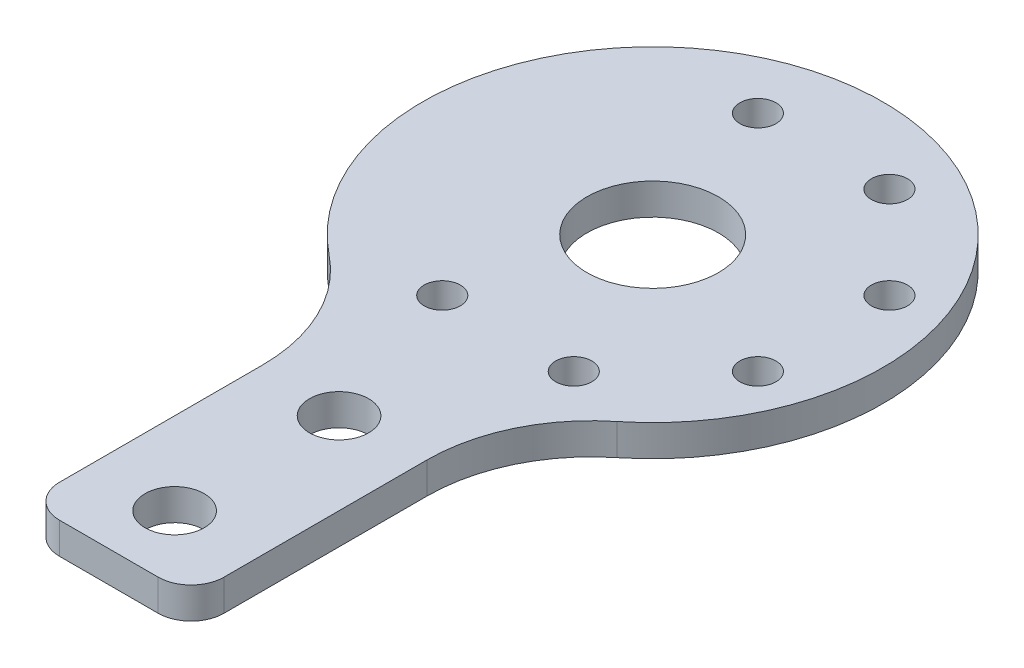
SolidWorks part; units mm, degrees
material "1060 Alloy"
ref_plane "Front Plane" through (0, 0, 0) normal (0, 0, 1) x (1, 0, 0)
ref_plane "Top Plane" through (0, 0, 0) normal (0, 1, 0) x (1, 0, 0)
ref_plane "Right Plane" through (0, 0, 0) normal (1, 0, 0) x (0, 0, -1)
sketch "Sketch1" plane through (0, 0, 0) normal (0, 1, 0) x (1, 0, 0)
  line L0 (-12.5, -82.6917) -> (12.5, -82.6917)
  line L1 (12.5, -82.6917) -> (12.5, -32.6917)
  line L2 (-12.5, -82.6917) -> (-12.5, -32.6917)
  arc A0 (12.5, -32.6917) -> (-12.5, -32.6917) centre (0, 0) ccw
  point P5 (0, -82.6917)
  dimension "D2" = 70
  dimension "D1" = 25
  dimension "D3" = 50
extrude "Boss-Extrude1" add sketch "Sketch1" along normal blind 4.7625 contours A0 L2 L0 L1
sketch "Sketch2" plane through (0, 0, 0) normal (0, -1, 0) x (1, 0, 0)
  line L0 (2.6194, 0) -> (-2.6194, 0) construction
  point P2 (0, 0)
  point P5 (-8, 24)
  point P13 (12, 24)
  point P14 (26, 10)
  point P22 (26, -10)
  point P23 (12, -24)
  point P24 (-8, -24)
  dimension "D2" = 26
  dimension "D1" = 8
  dimension "D3" = 20
  dimension "D4" = 10
  dimension "D5" = 24
sketch "Sketch5" plane through (0, 0, 0) normal (0, -1, 0) x (1, 0, 0)
  circle A0 centre (0, 0) radius 10
  dimension "D1" = 20
extrude "Cut-Extrude1" cut sketch "Sketch5" against normal through all
sketch "Sketch6" plane through (0, 0, 0) normal (0, -1, 0) x (1, 0, 0)
  line L0 (0, 82.6917) -> (0, 47.6917) construction
  line L1 (-12.5, 82.6917) -> (12.5, 82.6917) construction
  point P5 (0, 72.6917)
  dimension "D1" = 25
  dimension "D2" = 10
hole_wizard "M8 Clearance Hole1" positions "Sketch7" profile "Sketch8" hole size "M8" standard "ANSI Metric" end condition through all
sketch "Sketch7" plane through (0, 0, 0) normal (0, -1, 0) x (-1, 0, 0)
  point P0 (0, -47.6917)
  point P3 (0, -72.6917)
sketch "Sketch8" plane through (0, 0, 47.6917) normal (1, 0, 0) x (0, 0, -1)
  line L0 (0, 0) -> (0, 4.7625)
  line L1 (0, 4.7625) -> (4.5, 4.7625)
  line L2 (4.5, 4.7625) -> (4.5, 0)
  line L5 (4.5, 0) -> (0, 0)
  line L11 (0, -6.35) -> (0, 107.95) construction
  dimension "Thru Hole Dia." = 9
  dimension "Thru Hole Depth" = 4.7625
fillet "Fillet1" radius 25 2 edges at (-12.5, 2.3813, 32.6917) (12.5, 2.3813, 32.6917)
hole_wizard "M5 Clearance Hole1" positions "Sketch9" profile "Sketch10" hole size "M5" standard "ANSI Metric" end condition through all
sketch "Sketch9" plane through (0, 0, 0) normal (0, -1, 0) x (-1, 0, 0)
  point P18 (-12, 24)
  point P21 (8, 24)
  point P27 (-26, 10)
  point P30 (-26, -10)
  point P33 (-12, -24)
  point P36 (8, -24)
sketch "Sketch10" plane through (12, 0, -24) normal (1, 0, 0) x (0, 0, -1)
  line L0 (0, 0) -> (0, 4.7625)
  line L1 (0, 4.7625) -> (2.75, 4.7625)
  line L2 (2.75, 4.7625) -> (2.75, 0.025)
  line L3 (2.75, 0.025) -> (2.775, 0)
  line L5 (2.775, 0) -> (0, 0)
  line L6 (-2.75, 0.025) -> (-2.775, 0) construction
  line L11 (0, -6.35) -> (0, 107.95) construction
  dimension "Thru Hole Dia." = 5.5
  dimension "Thru Hole Depth" = 4.7625
  dimension "Near C'Sink Dia." = 5.55
  dimension "Near C'Sink Angle" = 90
fillet "Fillet2" radius 5 2 edges at (-12.5, 2.3813, 82.6917) (12.5, 2.3813, 82.6917)
